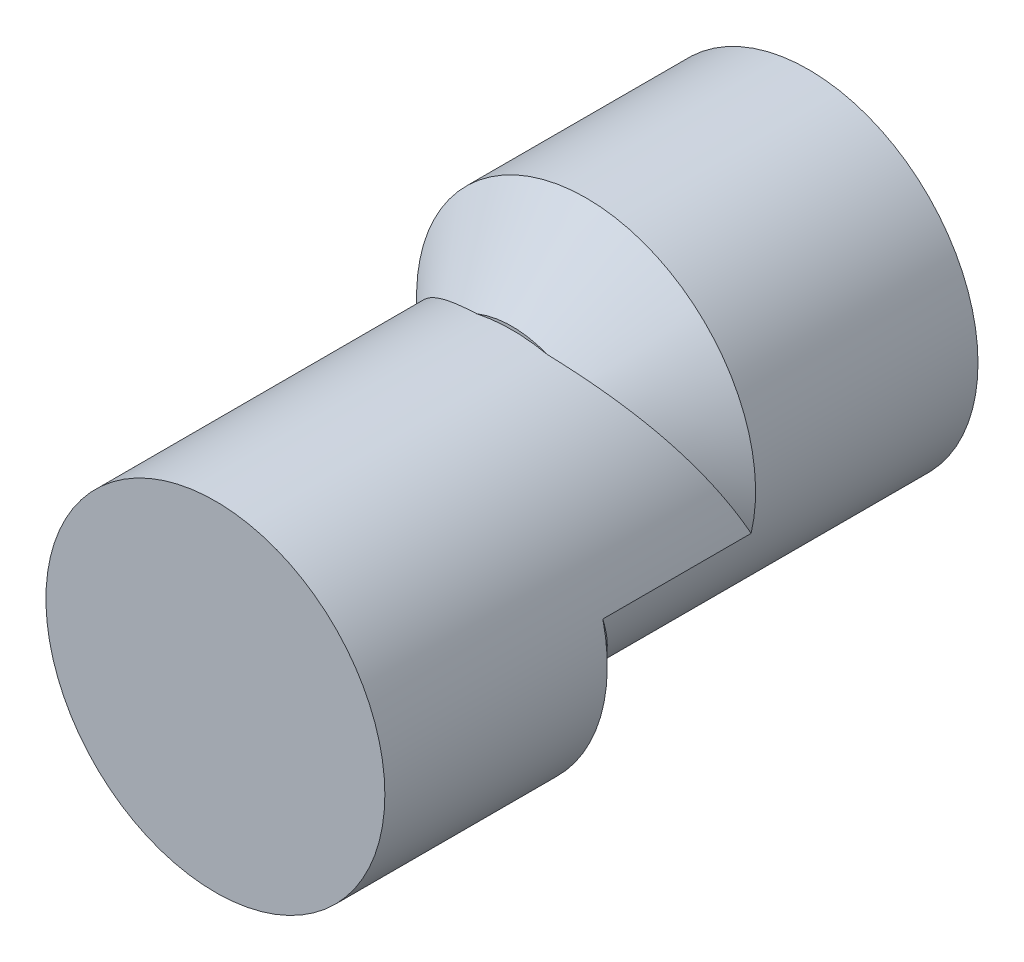
SolidWorks part; units mm, degrees
ref_plane "Plan de face" through (0, 0, 0) normal (0, 0, 1) x (1, 0, 0)
ref_plane "Plan de dessus" through (0, 0, 0) normal (0, 1, 0) x (1, 0, 0)
ref_plane "Plan de droite" through (0, 0, 0) normal (1, 0, 0) x (0, 0, -1)
sketch "Esquisse1" plane through (0, 0, 0) normal (0, 0, 1) x (1, 0, 0)
  circle A1 centre (0, 0.8221) radius 4
  dimension "D3" = 8
extrude "Boss.-Extru.1" add sketch "Esquisse1" along normal blind 7
sketch "Esquisse2" plane through (0, 0, 7) normal (0, 0, 1) x (1, 0, 0)
  circle A0 centre (0, -1) radius 4
  dimension "D1" = 8
  dimension "D2" = 1
extrude "Boss.-Extru.2" add sketch "Esquisse2" along normal blind 7
sketch "Esquisse3" plane through (0, 0, 14) normal (0, 0, 1) x (1, 0, 0)
  line L0 (-1.5, 2) -> (1.5, 2) construction
  line L1 (-1.5166, 2.05) -> (1.5166, 2.05)
  arc A0 (-1.5, 2) -> (1.5, 2) centre (0, 0) ccw construction
  arc A1 (-1.5166, 2.05) -> (1.5166, 2.05) centre (0, 0) ccw
  dimension "D1" = 5
  dimension "D2" = 2
  dimension "D3" = 0.05
extrude "Enlèv. mat.-Extru.1" cut sketch "Esquisse3" against normal through all from offset 2 offset against normal yes
chamfer "Chanfrein2" distance 1.75 angle 45 1 edges at (0, 4.8221, 7)
chamfer "Chanfrein4" distance 1.75 angle 45 1 edges at (0, -5, 7)
